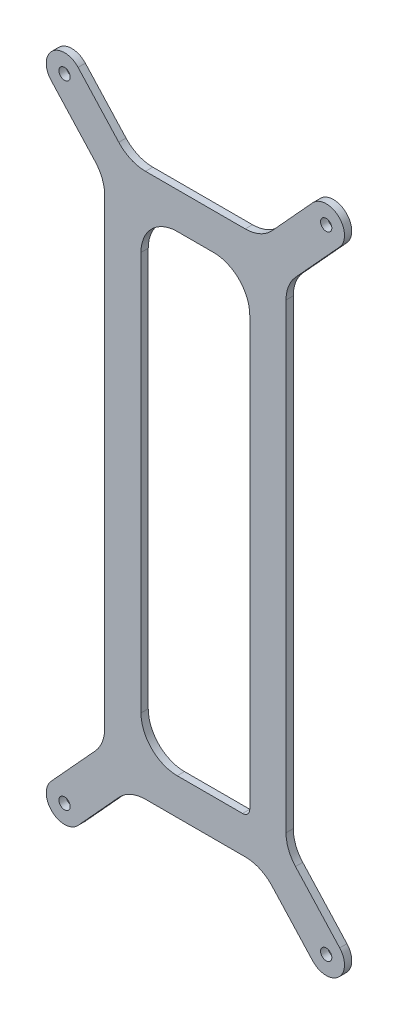
SolidWorks part; units mm, degrees
material "Hexcel AS4C (3000 Filaments)"
ref_plane "Front Plane" through (0, 0, 0) normal (0, 0, 1) x (1, 0, 0)
ref_plane "Top Plane" through (0, 0, 0) normal (0, 1, 0) x (1, 0, 0)
ref_plane "Right Plane" through (0, 0, 0) normal (1, 0, 0) x (0, 0, -1)
sketch "Sketch1" plane through (0, 0, 0) normal (0, 0, 1) x (1, 0, 0)
  line L24 (-15, 55) -> (-15, -55)
  line L25 (-25, 63.6326) -> (-25, -63.6326)
  line L26 (25, 63.6326) -> (25, -63.6326)
  line L27 (5, -65) -> (13, -65)
  line L28 (15, -63) -> (15, -55)
  line L32 (-5, -65) -> (5, -65)
  line L39 (-13.7508, -75) -> (13.7508, -75)
  line L42 (-13.7508, 75) -> (13.7508, 75)
  line L45 (39.8075, 83.7218) -> (27.6169, 70.3772)
  line L46 (15, -55) -> (15, 55)
  line L47 (-5, 65) -> (5, 65)
  line L49 (-15, -65) -> (15, -65) construction
  line L50 (-15, -65) -> (-15, 65) construction
  line L51 (15, -65) -> (15, 65) construction
  line L52 (-15, 65) -> (15, 65) construction
  line L53 (32.3506, 90.5338) -> (21.1339, 78.2554)
  line L54 (-32.3506, 90.5338) -> (-21.1339, 78.2554)
  line L55 (-39.8075, 83.7218) -> (-27.6169, 70.3772)
  line L56 (39.8075, -83.7218) -> (27.6169, -70.3772)
  line L57 (32.3506, -90.5338) -> (21.1339, -78.2554)
  line L58 (-32.3506, -90.5338) -> (-21.1339, -78.2554)
  line L59 (-39.8075, -83.7218) -> (-27.6169, -70.3772)
  line L60 (-25, -75) -> (-25, 75) construction
  line L61 (-25, -75) -> (25, -75) construction
  line L62 (25, -75) -> (25, 75) construction
  line L63 (-25, 75) -> (25, 75) construction
  arc A30 (-39.8075, 83.7218) -> (-32.3506, 90.5338) centre (-36.0791, 87.1278) cw
  arc A31 (32.3506, 90.5338) -> (39.8075, 83.7218) centre (36.0791, 87.1278) cw
  arc A36 (39.8075, -83.7218) -> (32.3506, -90.5338) centre (36.0791, -87.1278) cw
  arc A37 (-32.3506, -90.5338) -> (-39.8075, -83.7218) centre (-36.0791, -87.1278) cw
  arc A38 (13, -65) -> (15, -63) centre (13, -63) ccw
  circle A42 centre (-36.0791, 87.1278) radius 1.55
  circle A43 centre (36.0791, 87.1278) radius 1.55
  circle A45 centre (36.0791, -87.1278) radius 1.55
  circle A47 centre (-36.0791, -87.1278) radius 1.55
  arc A49 (-5, -65) -> (-15, -55) centre (-5, -55) cw
  arc A51 (15, 55) -> (5, 65) centre (5, 55) ccw
  arc A52 (-5, 65) -> (-15, 55) centre (-5, 55) ccw
  arc A53 (-25, -63.6326) -> (-27.6169, -70.3772) centre (-35, -63.6326) cw
  arc A54 (-21.1339, -78.2554) -> (-13.7508, -75) centre (-13.7508, -85) cw
  arc A55 (21.1339, -78.2554) -> (13.7508, -75) centre (13.7508, -85) ccw
  arc A56 (25, -63.6326) -> (27.6169, -70.3772) centre (35, -63.6326) ccw
  arc A57 (25, 63.6326) -> (27.6169, 70.3772) centre (35, 63.6326) cw
  arc A58 (13.7508, 75) -> (21.1339, 78.2554) centre (13.7508, 85) ccw
  arc A59 (-13.7508, 75) -> (-21.1339, 78.2554) centre (-13.7508, 85) cw
  arc A60 (-25, 63.6326) -> (-27.6169, 70.3772) centre (-35, 63.6326) ccw
  point P40 (0, 0)
  dimension "D1" = 2
  dimension "D6" = 10
  dimension "D7" = 10
  dimension "D8" = 10
extrude "Boss-Extrude1" add sketch "Sketch1" along normal blind 2
